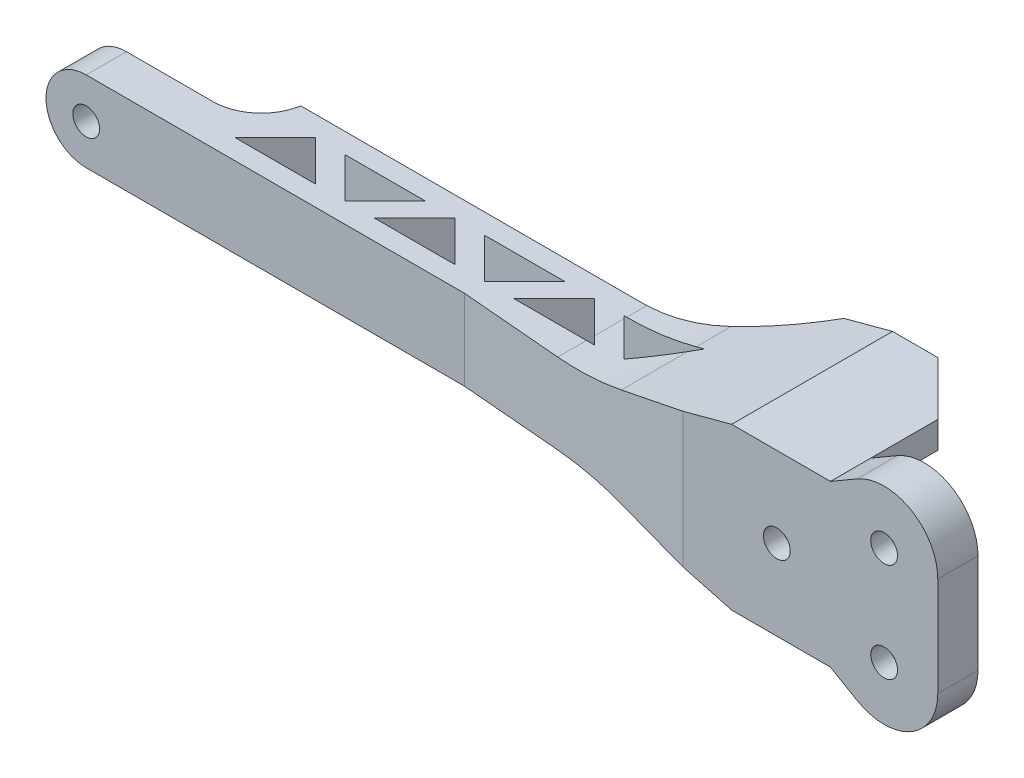
SolidWorks part; units mm, degrees
ref_plane "Front Plane" through (0, 0, 0) normal (0, 0, 1) x (1, 0, 0)
ref_plane "Top Plane" through (0, 0, 0) normal (0, 1, 0) x (1, 0, 0)
ref_plane "Right Plane" through (0, 0, 0) normal (1, 0, 0) x (0, 0, -1)
sketch "Sketch1" plane through (0, 0, 0) normal (0, 1, 0) x (1, 0, 0)
  line L0 (0, 0) -> (126.4393, 0)
  line L1 (180, 22.5) -> (215, 22.5)
  line L2 (215, 22.5) -> (235, 2.5)
  line L3 (235, 2.5) -> (235, -22.5)
  line L4 (235, -22.5) -> (275, -22.5)
  line L5 (275, -22.5) -> (275, -37.5)
  line L6 (275, -37.5) -> (180, -37.5)
  line L7 (180, -37.5) -> (91, -30)
  line L8 (91, -30) -> (-65, -30)
  line L9 (-65, -30) -> (-65, -15)
  line L10 (-65, -15) -> (-17.7482, -15)
  line L11 (-65, -22.5) -> (235, -22.5) construction
  line L12 (215, -37.5) -> (215, -8.413) construction
  line L13 (255, -37.5) -> (255, -8.413) construction
  line L14 (-2, -22.5) -> (13, -7.5)
  line L15 (13, -7.5) -> (28, -22.5)
  line L16 (28, -22.5) -> (-2, -22.5)
  line L17 (50, -22.5) -> (65, -7.5)
  line L18 (65, -7.5) -> (80, -22.5)
  line L19 (80, -22.5) -> (50, -22.5)
  line L20 (54, -7.5) -> (39, -22.5)
  line L21 (39, -22.5) -> (24, -7.5)
  line L22 (24, -7.5) -> (54, -7.5)
  line L23 (106, -7.5) -> (91, -22.5)
  line L24 (91, -22.5) -> (76, -7.5)
  line L25 (76, -7.5) -> (106, -7.5)
  line L26 (158, -7.5) -> (143, -22.5)
  line L27 (143, -22.5) -> (128, -7.5)
  line L28 (128, -7.5) -> (158, -7.5)
  line L29 (102, -22.5) -> (117, -7.5)
  line L30 (117, -7.5) -> (132, -22.5)
  line L31 (132, -22.5) -> (102, -22.5)
  line L32 (-50, -22.5) -> (-50, -7.5) construction
  arc A0 (126.4393, 0) -> (180, 22.5) centre (126.4393, 75) ccw
  arc A1 (-17.7482, -15) -> (0, 0) centre (-17.7482, 3) ccw
  dimension "D1" = 75
  dimension "D6" = 18
  dimension "D2" = 245
  dimension "D3" = 15
  dimension "D4" = 30
  dimension "D5" = 65
  dimension "D7" = 60
  dimension "D8" = 15
  dimension "D9" = 20
  dimension "D10" = 300
  dimension "D11" = 60
  dimension "D12" = 15
  dimension "D13" = 45
  dimension "D14" = 325
  dimension "D15" = 11
  dimension "D16" = 30
  dimension "D17" = 63
  dimension "D18" = 11
  dimension "D19" = 11
  dimension "D20" = 11
  dimension "D21" = 11
extrude "Boss-Extrude1" add sketch "Sketch1" along normal blind 77
sketch "Sketch2" plane through (0, 0, 0) normal (0, 0, -1) x (-1, 0, 0)
  line L0 (65, 38.5) -> (-275, 38.5) construction
  line L1 (65, 77) -> (65, 0) construction
  line L2 (-275, 77) -> (-275, 0) construction
  line L3 (-154.8819, 20.0926) -> (-198.146, 8.5)
  line L4 (50, 23.5) -> (-129, 23.5)
  line L5 (50, 23.5) -> (50, 53.5)
  line L6 (50, 53.5) -> (-129, 53.5)
  line L7 (-129, 23.5) -> (-129, 53.5)
  line L8 (-198.146, 8.5) -> (-235, 8.5)
  line L9 (-235, 8.5) -> (-235, 18.5)
  line L10 (-235, 18.5) -> (-205, 18.5)
  line L11 (-190, 33.5) -> (-190, 57.3352) construction
  line L12 (-255, 57) -> (-255, 20) construction
  line L13 (-235, 57) -> (-235, 20)
  line L14 (-275, 57) -> (-275, 20)
  line L15 (-244.9389, 2.7149) -> (-235, 8.5)
  line L16 (-244.9389, 74.2851) -> (-235, 68.5)
  line L17 (-235, 68.5) -> (-235, 58.5)
  line L18 (-235, 58.5) -> (-205, 58.5)
  line L19 (-198.146, 68.5) -> (-235, 68.5)
  line L20 (-154.8819, 56.9074) -> (-198.146, 68.5)
  line L21 (-190, 33.5) -> (-190, 43.5)
  line L22 (65, 0) -> (65, 77)
  line L23 (65, 77) -> (-275, 77)
  line L24 (-275, 77) -> (-275, 0)
  line L25 (-275, 0) -> (65, 0)
  circle A0 centre (50, 38.5) radius 15
  arc A1 (-129, 23.5) -> (-154.8819, 20.0926) centre (-129, -76.5) ccw
  arc A2 (-205, 18.5) -> (-190, 33.5) centre (-205, 33.5) ccw
  arc A3 (-235, 57) -> (-275, 57) centre (-255, 57) ccw
  arc A4 (-275, 20) -> (-235, 20) centre (-255, 20) ccw
  arc A5 (-205, 58.5) -> (-190, 43.5) centre (-205, 43.5) cw
  arc A6 (-129, 53.5) -> (-154.8819, 56.9074) centre (-129, 153.5) cw
  point P22 (-255, 38.5)
  line M9 (-126.4393, 0) -> (0, 0)
  line M10 (0, 0) -> (0, 77)
  line M11 (0, 77) -> (-126.4393, 77)
  line M12 (-126.4393, 77) -> (-126.4393, 0)
  dimension "D1" = 30
  dimension "D3" = 100
  dimension "D4" = 15
  dimension "D8" = 45
  dimension "D10" = 20
  dimension "D11" = 77
  dimension "D2" = 179
  dimension "D5" = 165
  dimension "D6" = 20
  dimension "D7" = 30
  dimension "D9" = 300
extrude "Cut-Extrude1" cut sketch "Sketch2" against normal through all both and the other way through all contours L4 M10 M12 M9 | A0 L4 L25 L22 M10 | A0 L22 L23 L6 M10 | L6 M10 M11 M12 | A6 L6 L23 A3 L16 L19 L20 M12 | A4 L25 L4 A1 L3 L8 L15 M12 | A4 L24 L25 | A3 L23 L24 region at (171.4464, 8.1743, 0) region at (63.2196, 11.75, 0) region at (171.4464, 68.8257, 0) region at (-33.3932, 12.2127, 0) region at (63.2196, 65.25, 0) region at (270.5326, 4.4674, 0) region at (-33.3932, 64.7873, 0) region at (270.5326, 72.5326, 0)
extrude "Cut-Extrude2" cut sketch "Sketch2<3>" against normal up to surface (22.5 mm away) and the other way through all contours A5 L18 L17 L16 A3 L13 A4 L15 L9 L10 A2 L21 region at (214.1581, 38.5, 0) up to face at (253.313, 38.5, 22.5)
sketch "Sketch2<3>" plane through (0, 0, 0) normal (0, 0, -1) x (-1, 0, 0) same geometry as "Sketch2"
sketch "Sketch3" plane through (0, 0, 22.5) normal (0, 0, -1) x (-1, 0, 0)
  line L0 (-275, 38.5) -> (97.8605, 38.5) construction
  line L1 (-275, 57) -> (-275, 20) construction
  line L3 (-235, 8.5) -> (-215, 8.5) construction
  circle A0 centre (-215, 38.5) radius 5
  circle A1 centre (-255, 20.04) radius 5
  circle A2 centre (-255, 56.96) radius 5
  circle A3 centre (50, 38.5) radius 5
  dimension "D1" = 48.46
  dimension "D4" = 10
  dimension "D2" = 20
  dimension "D3" = 60
extrude "Cut-Extrude3" cut sketch "Sketch3" against normal through all and the other way through all
sketch "Sketch4" plane through (0, 0, 22.5) normal (0, 0, -1) x (-1, 0, 0)
  circle A0 centre (-215, 38.5) radius 5 construction
  circle A1 centre (-255, 20.04) radius 5 construction
  circle A2 centre (-255, 56.96) radius 5 construction
  circle A3 centre (-215, 38.5) radius 5
  circle A4 centre (-255, 20.04) radius 5
  circle A5 centre (-255, 56.96) radius 5
  circle A6 centre (-215, 38.5) radius 7.5
  circle A7 centre (-255, 20.04) radius 7.5
  circle A8 centre (-255, 56.96) radius 7.5
  dimension "D1" = 2.5
extrude "Cut-Extrude4" cut sketch "Sketch4" against normal blind 8
